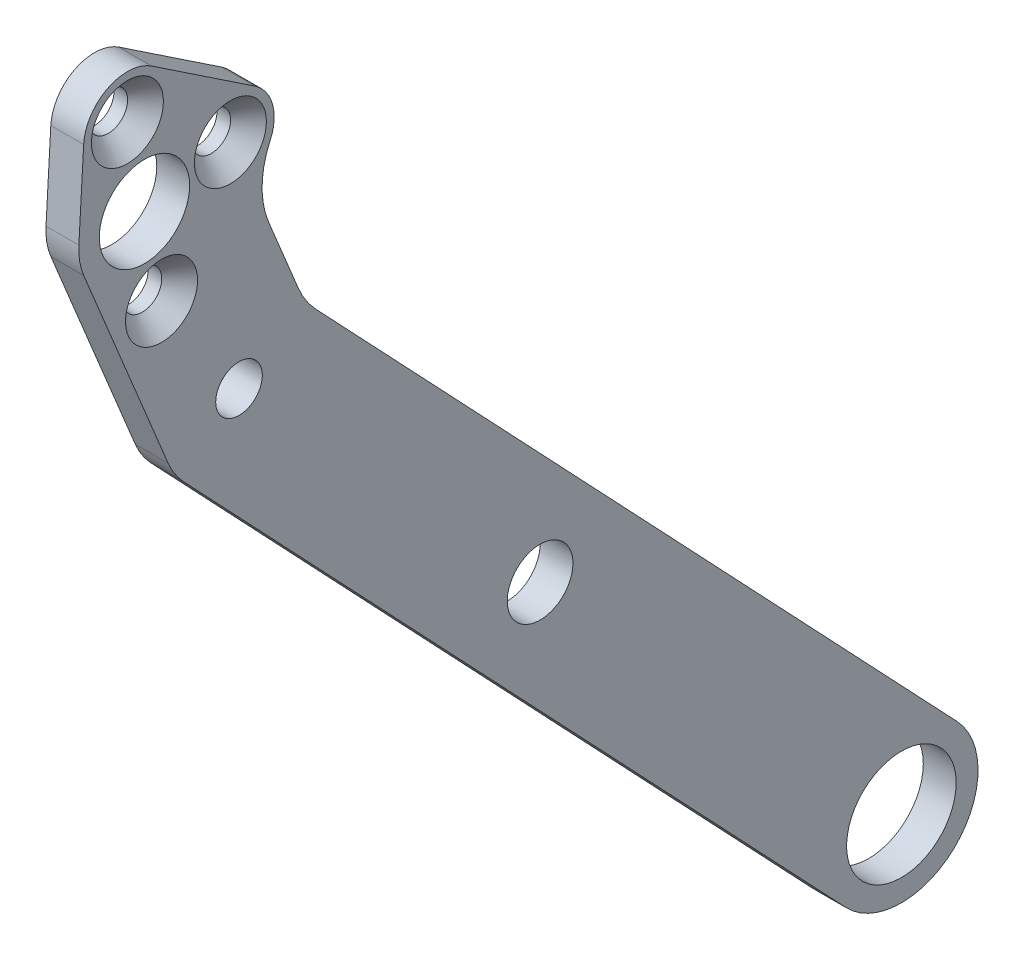
SolidWorks part; units mm, degrees
ref_plane "Front Plane" through (0, 0, 0) normal (0, 0, 1) x (1, 0, 0)
ref_plane "Top Plane" through (0, 0, 0) normal (0, 1, 0) x (1, 0, 0)
ref_plane "Right Plane" through (0, 0, 0) normal (1, 0, 0) x (0, 0, -1)
sketch "Sketch1" plane through (0, 0, 0) normal (1, 0, 0) x (0, 0, -1)
  line L1 (-1394.4671, 276.8368) -> (-1298.4468, 175.3666) construction
  line L3 (-1394.4671, 276.8368) -> (-1298.4468, 175.3666)
  line L8 (-1378.3241, 292.1128) -> (-1282.3038, 190.6425) construction
  line L9 (-1378.3241, 292.1128) -> (-1282.3038, 190.6425)
  circle A0 centre (-1386.3956, 284.4748) radius 11.1125 construction
  arc A1 (-1378.3241, 292.1128) -> (-1394.4671, 276.8368) centre (-1386.3956, 284.4748) ccw
  circle A6 centre (-1290.3753, 183.0046) radius 11.1125 construction
  arc A7 (-1298.4468, 175.3666) -> (-1282.3038, 190.6425) centre (-1290.3753, 183.0046) ccw
  circle A8 centre (-1290.3753, 183.0046) radius 7.9375 construction
  circle A9 centre (-1290.3753, 183.0046) radius 7.9375
extrude "Boss-Extrude1" add sketch "Sketch1" against normal up to vertex from vertex
hole_wizard "1/4 Clearance Hole1" positions "Sketch2" profile "Sketch3" hole size "1/4" standard "ANSI Inch" end condition through all
sketch "Sketch2" plane through (27.6416, 0, 0) normal (-1, 0, 0) x (0, 0, 1)
  point P3 (1386.3956, 284.4748)
sketch "Sketch3" plane through (27.6416, 284.4748, 1386.3956) normal (0, 1, 0) x (0, 0, 1)
  line L0 (0, 0) -> (0, 4.7625)
  line L1 (0, 4.7625) -> (3.3782, 4.7625)
  line L2 (3.3782, 4.7625) -> (3.3782, 0)
  line L5 (3.3782, 0) -> (0, 0)
  line L11 (0, -6.35) -> (0, 107.95) construction
  dimension "Thru Hole Dia." = 6.7564
  dimension "Thru Hole Depth" = 4.7625
sketch "Sketch4" plane through (0, 0, 0) normal (1, 0, 0) x (0, 0, -1)
  circle A0 centre (-1342.75, 238.352) radius 4.7625 construction
  circle A1 centre (-1342.75, 238.352) radius 4.7625
extrude "Cut-Extrude1" cut sketch "Sketch4" against normal through all both and the other way through all
sketch "Sketch5" plane through (0, 0, 0) normal (1, 0, 0) x (0, 0, -1)
  line L0 (-1408.9153, 326.3708) -> (-1409.6107, 314.0937) construction
  line L1 (-1399.0463, 331.2906) -> (-1384.1152, 321.3086) construction
  line L2 (-1385.0036, 310.2548) -> (-1376.9074, 290.6157) construction
  line L3 (-1408.907, 309.9248) -> (-1396.6693, 280.2395) construction
  line L4 (-1408.9153, 326.3708) -> (-1409.6107, 314.0937)
  line L5 (-1399.0463, 331.2906) -> (-1384.1152, 321.3086)
  line L6 (-1385.0036, 310.2548) -> (-1376.9074, 290.6157)
  line L7 (-1408.907, 309.9248) -> (-1396.6693, 280.2395)
  line L8 (-1378.3241, 292.1128) -> (-1282.3038, 190.6425) construction
  line L9 (-1378.3241, 292.1128) -> (-1376.9074, 290.6157)
  circle A0 centre (-1400.1009, 313.5551) radius 9.525 construction
  circle A1 centre (-1402.5755, 326.0117) radius 6.35 construction
  circle A2 centre (-1387.6444, 316.0296) radius 6.35 construction
  circle A3 centre (-1386.3956, 284.4748) radius 11.1125 construction
  arc A4 (-1409.6107, 314.0937) -> (-1408.907, 309.9248) centre (-1400.1009, 313.5551) ccw
  arc A5 (-1399.0463, 331.2906) -> (-1408.9153, 326.3708) centre (-1402.5755, 326.0117) ccw
  arc A6 (-1385.0036, 310.2548) -> (-1384.1152, 321.3086) centre (-1387.6444, 316.0296) ccw
  arc A7 (-1378.3241, 292.1128) -> (-1396.6693, 280.2395) centre (-1386.3956, 284.4748) ccw
extrude "Boss-Extrude2" add sketch "Sketch5" along normal up to vertex (32.4041 mm away) from vertex at 27.6416
hole_wizard "1/2 Clearance Hole1" positions "Sketch7" profile "Sketch8" hole size "1/2" standard "ANSI Inch" end condition through all
sketch "Sketch7" plane through (32.4041, 0, 0) normal (1, 0, 0) x (0, 0, -1)
  point P0 (-1400.1009, 313.5551)
sketch "Sketch8" plane through (32.4041, 313.5551, 1400.1009) normal (0, 1, 0) x (0, 0, -1)
  line L0 (0, 0) -> (0, 4.7625)
  line L1 (0, 4.7625) -> (6.5481, 4.7625)
  line L2 (6.5481, 4.7625) -> (6.5481, 0)
  line L5 (6.5481, 0) -> (0, 0)
  line L11 (0, -6.35) -> (0, 107.95) construction
  dimension "Thru Hole Dia." = 13.0962
  dimension "Thru Hole Depth" = 4.7625
hole_wizard "CSK for #10 Flat Head Socket Cap Screw1" positions "Sketch9" profile "Sketch10" countersink size "#10" standard "ANSI Inch" end condition through all
sketch "Sketch9" plane through (32.4041, 0, 0) normal (1, 0, 0) x (0, 0, -1)
  point P0 (-1402.5755, 326.0117)
  point P3 (-1387.6444, 316.0296)
  point P6 (-1397.6264, 301.0985)
sketch "Sketch10" plane through (32.4041, 326.0117, 1402.5755) normal (0, 1, 0) x (0, 0, -1)
  line L0 (0, 0) -> (0, 4.7625)
  line L1 (0, 4.7625) -> (2.8067, 4.7625)
  line L2 (2.8067, 4.7625) -> (2.8067, 2.7758)
  line L3 (2.8067, 2.7758) -> (5.2197, 0)
  line L5 (5.2197, 0) -> (0, 0)
  line L6 (-2.8067, 2.7758) -> (-5.2197, 0) construction
  line L11 (0, -6.35) -> (0, 107.95) construction
  dimension "Thru Hole Dia." = 5.6134
  dimension "Thru Hole Depth" = 4.7625
  dimension "Near C'Sink Dia." = 10.4394
  dimension "Near C'Sink Angle" = 82
fillet "Fillet1" radius 12.7 2 edges at (30.0229, 290.6157, 1376.9074) (30.0229, 310.2548, 1385.0036)
